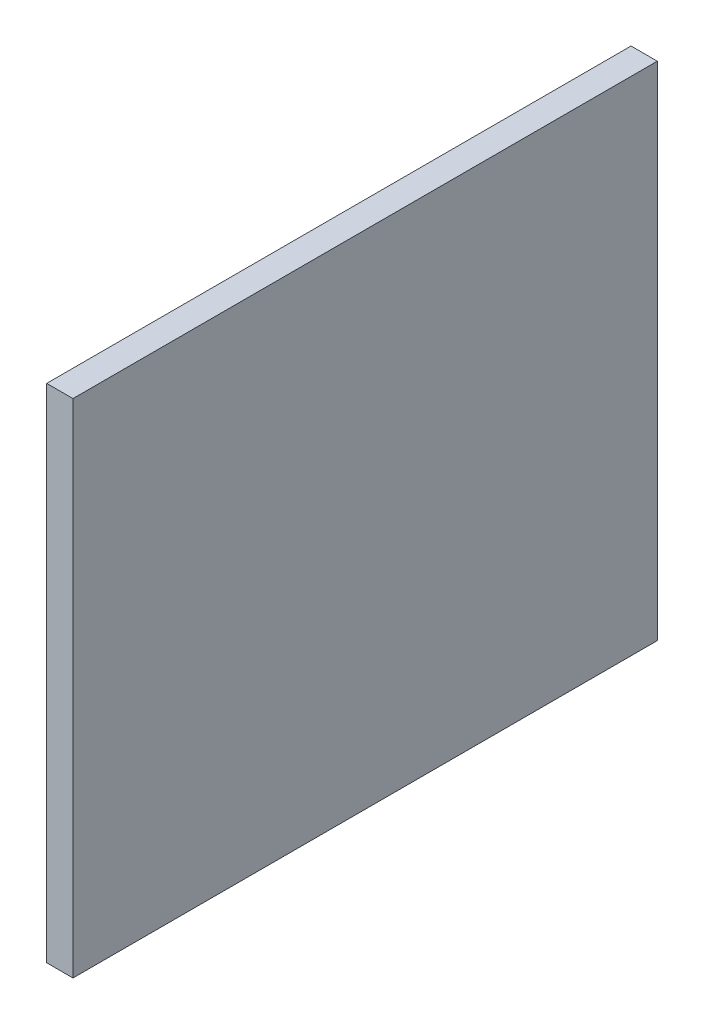
SolidWorks part; units mm, degrees
ref_plane "Front" through (0, 0, 0) normal (0, 0, 1) x (1, 0, 0)
ref_plane "Top" through (0, 0, 0) normal (0, 1, 0) x (1, 0, 0)
ref_plane "Right" through (0, 0, 0) normal (1, 0, 0) x (0, 0, -1)
sketch "Sketch1" plane through (0, 0, 0) normal (1, 0, 0) x (0, 0, -1)
  line L1 (-200, -171.75) -> (200, -171.75)
  line L2 (-200, -171.75) -> (-200, 171.75)
  line L3 (-200, 171.75) -> (200, 171.75)
  line L4 (200, -171.75) -> (200, 171.75)
  line L5 (-200, -171.75) -> (200, 171.75) construction
  line L6 (-200, 171.75) -> (200, -171.75) construction
  point P0 (0, 0)
  dimension "D1" = 400
  dimension "D2" = 343.5
extrude "Boss-Extrude1" add sketch "Sketch1" along normal blind 18
